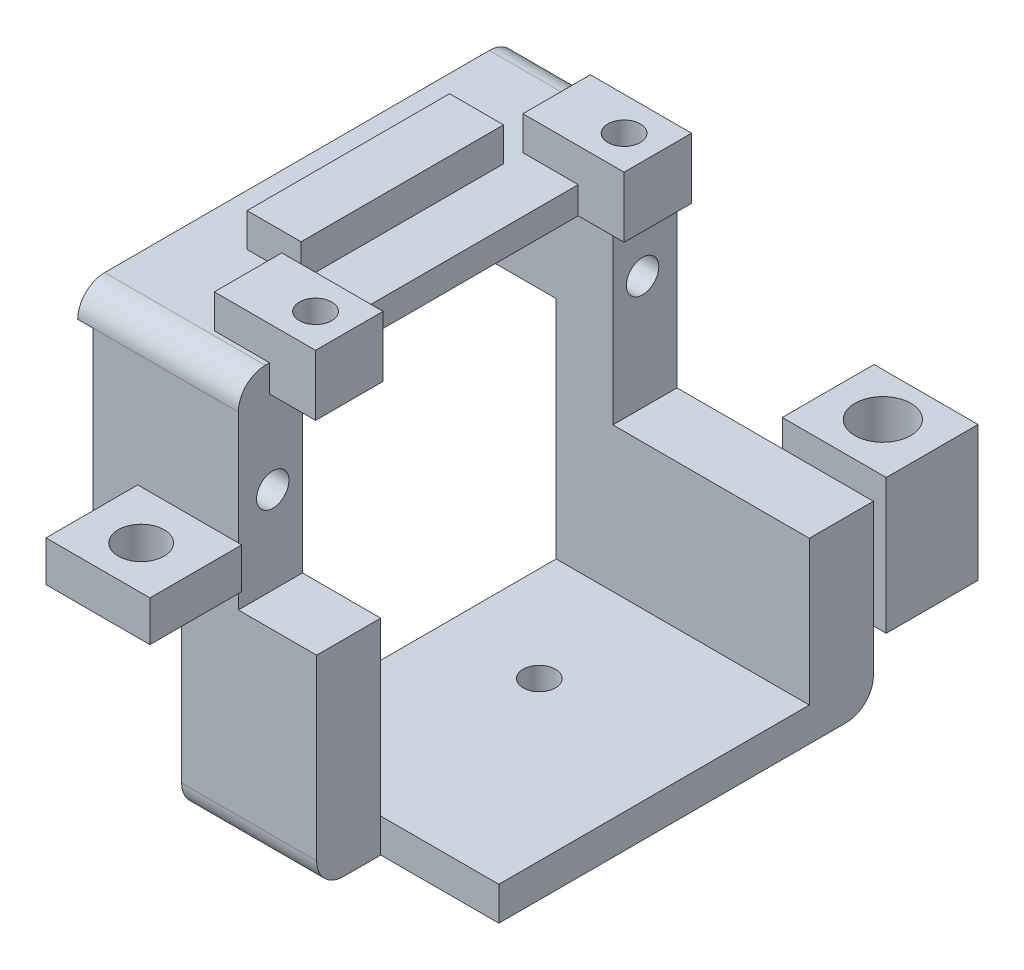
SolidWorks part; units mm, degrees
ref_plane "Front Plane" through (0, 0, 0) normal (0, 0, 1) x (1, 0, 0)
ref_plane "Top Plane" through (0, 0, 0) normal (0, 1, 0) x (1, 0, 0)
ref_plane "Right Plane" through (0, 0, 0) normal (1, 0, 0) x (0, 0, -1)
sketch "Sketch1" plane through (0, 0, 0) normal (0, 1, 0) x (1, 0, 0)
  line L0 (-1.1, 16.25) -> (-1.1, 11.5)
  line L1 (-17.65, -16.25) -> (17.65, -16.25)
  line L2 (-17.65, -16.25) -> (-17.65, 16.25)
  line L3 (-17.65, 16.25) -> (17.65, 16.25)
  line L4 (17.65, -16.25) -> (17.65, 16.25)
  line L5 (-17.65, -16.25) -> (17.65, 16.25) construction
  line L6 (-17.65, 16.25) -> (17.65, -16.25) construction
  line L7 (-1.1, 11.5) -> (17.65, 11.5)
  line L8 (-1.1, -16.25) -> (-1.1, -11.5)
  line L9 (-1.1, -11.5) -> (17.65, -11.5)
  line L10 (-1.1, 11.5) -> (-1.1, -11.5) construction
  line L11 (8.9, -11.5) -> (8.9, -16.25)
  line L12 (-8.8, 16.25) -> (-8.8, 11.5)
  line L13 (-8.8, 11.5) -> (-3.8, 11.5)
  line L14 (-3.8, 11.5) -> (-3.8, 16.25)
  line L15 (-3.8, -16.25) -> (-3.8, -11.5)
  line L16 (-3.8, -11.5) -> (-8.8, -11.5)
  line L17 (-8.8, -11.5) -> (-8.8, -16.25)
  line L18 (-8.8, 11.5) -> (-8.8, -11.5)
  line L19 (18.6, 16.25) -> (18.6, 23.05)
  line L20 (18.6, 23.05) -> (10.9, 23.05)
  line L21 (10.9, 23.05) -> (10.9, 16.25)
  line L22 (-4.35, -16.25) -> (-4.35, -23.05)
  line L23 (-4.35, -23.05) -> (3.35, -23.05)
  line L24 (3.35, -23.05) -> (3.35, -16.25)
  line L25 (18.6, 16.25) -> (10.9, 16.25)
  line L28 (-1.1, 11.5) -> (-1.1, -11.5)
  circle A0 centre (14.75, 19.85) radius 2.075
  circle A2 centre (-0.5, -19.85) radius 1.7
  point P0 (0, 0)
  point P11 (-1.1, 0)
  point P31 (14.75, 23.05)
  point P45 (-0.5, -23.05)
  dimension "D11" = 4.15
  dimension "D19" = 3.4
  dimension "D1" = 32.5
  dimension "D2" = 23
  dimension "D3" = 8.75
  dimension "D4" = 10
  dimension "D5" = 16.55
  dimension "D6" = 2.7
  dimension "D7" = 5
  dimension "D8" = 14.75
  dimension "D9" = 7.7
  dimension "D10" = 6.8
  dimension "D12" = 0.5
  dimension "D13" = 19.85
  dimension "D16" = 7.7
  dimension "D17" = 6.8
  dimension "D20" = 19.85
extrude "Boss-Extrude1" add sketch "Sketch1" against normal blind 2.5 contours L7 L28 L9 L4 | L0 L7 L4 L3 | L11 L9 L8 L1 region at (8.275, 0, -13.875) region at (8.275, 0, 0) region at (3.9, 0, 13.875)
extrude "Boss-Extrude2" add sketch "Sketch1<3>" along normal blind 12.7 contours L0 L7 L4 L3 | L11 L9 L8 L1 region at (8.275, 0, -13.875) region at (3.9, 0, 13.875)
sketch "Sketch1<3>" plane through (0, 0, 0) normal (0, 1, 0) x (1, 0, 0) same geometry as "Sketch1"
sketch "Sketch3" plane through (0, 0, 0) normal (0, 1, 0) x (1, 0, 0)
  line L0 (3.1, 16.25) -> (3.1, 11.5)
  line L1 (-17.65, 16.25) -> (17.65, 16.25) construction
  line L2 (-1.1, 11.5) -> (17.65, 11.5) construction
  line L3 (3.1, 11.5) -> (-17.65, 11.5)
  line L4 (-17.65, -16.25) -> (-17.65, 16.25) construction
  line L5 (3.1, -16.25) -> (3.1, -11.5)
  line L6 (-17.65, -16.25) -> (17.65, -16.25) construction
  line L7 (-1.1, -11.5) -> (17.65, -11.5) construction
  line L8 (3.1, -11.5) -> (-17.65, -11.5)
  line L9 (3.1, 11.5) -> (3.1, -11.5)
  line L10 (-7.65, -11.5) -> (-7.65, -16.275)
  line L11 (3.1, 16.25) -> (-17.65, 16.25)
  line L12 (-17.65, 16.25) -> (-17.65, 11.5)
  line L13 (-17.65, -11.5) -> (-17.65, -16.25)
  line L14 (-17.65, -16.25) -> (3.1, -16.25)
  line L15 (-8.8, 11.5) -> (-8.8, -11.5)
  line L16 (-8.8, 11.5) -> (-8.8, 16.25)
  line L17 (-8.8, -11.5) -> (-8.8, -16.25)
  dimension "D1" = 20.75
  dimension "D2" = 10
extrude "Boss-Extrude3" add sketch "Sketch3" along normal blind 12.7 from surface contours L11 L12 L3 L0 | L10 L14 L5 L8 region at (-2.85, 0, -13.875) region at (-2.275, 0, 13.875) starting at face at (8.275, 12.7, -13.875)
extrude "Boss-Extrude4" add sketch "Sketch3<3>" along normal blind 2 from surface contours L16 L3 L0 L11 | L3 L15 L8 L9 | L10 L14 L5 L8 | L8 L17 L14 L10 region at (-2.85, 0, -13.875) region at (-2.85, 0, 0) region at (-2.275, 0, 13.875) region at (-8.225, 0, 13.875) starting at face at (-2.275, 25.4, 13.875)
sketch "Sketch3<3>" plane through (0, 0, 0) normal (0, 1, 0) x (1, 0, 0) same geometry as "Sketch3"
sketch "Sketch2" plane through (0, 0, 0) normal (1, 0, 0) x (0, 0, -1)
  line L0 (13.7, 6.45) -> (-13.7, 6.45) construction
  line L1 (-13.7, 19.15) -> (13.7, 19.15) construction
  circle A0 centre (13.7, 6.45) radius 1.2
  circle A1 centre (-13.7, 6.45) radius 1.2
  circle A2 centre (-13.7, 19.15) radius 1.2
  circle A3 centre (13.7, 19.15) radius 1.2
  point P4 (0, 6.45)
  dimension "D1" = 2.4
  dimension "D2" = 2.4
  dimension "D6" = 2.4
  dimension "D7" = 2.4
  dimension "D3" = 27.4
  dimension "D4" = 6.45
  dimension "D5" = 6.45
extrude "Cut-Extrude1" cut sketch "Sketch2" along normal blind 8 from surface contours A1 | A0 region at (0, 6.45, -13.7) region at (0, 6.45, 13.7) starting at face at (-1.1, 5.725, 0)
extrude "Cut-Extrude2" cut sketch "Sketch2<3>" against normal blind 8 from surface contours A3 | A2 region at (0, 19.15, 13.7) region at (0, 19.15, -13.7) starting at face at (3.1, 19.55, 0)
sketch "Sketch2<3>" plane through (0, 0, 0) normal (1, 0, 0) x (0, 0, -1) same geometry as "Sketch2"
extrude "Boss-Extrude5" add sketch "Sketch1<4>" against normal blind 3 from offset 17 contours L23 L24 L1 L22 A2 region at (1.125, 0, 16.3527)
sketch "Sketch1<4>" plane through (0, 0, 0) normal (0, 1, 0) x (1, 0, 0) same geometry as "Sketch1"
extrude "Boss-Extrude6" add sketch "Sketch1<7>" against normal blind 10 from surface contours L20 L21 L3 L19 A0 region at (11.0027, 0, -19.65) starting at face at (10.375, 12.7, -13.875)
sketch "Sketch1<7>" plane through (0, 0, 0) normal (0, 1, 0) x (1, 0, 0) same geometry as "Sketch1"
fillet "Fillet1" radius 2 4 edges at (3.9, -2.5, 16.25) (-2.85, 27.4, 16.25) (8.275, -2.5, -16.25) (-2.85, 27.4, -16.25)
sketch "Sketch5" plane through (0, 0, 0) normal (0, 1, 0) x (1, 0, 0)
  line L1 (17.65, 16.25) -> (3.1, 16.25)
  line L2 (17.65, 16.25) -> (17.65, 11.5)
  line L3 (17.65, 11.5) -> (3.1, 11.5)
  line L4 (3.1, 16.25) -> (3.1, 11.5)
extrude "Cut-Extrude3" cut sketch "Sketch5" against normal blind 2 from surface starting at face at (12.5625, 12.7, -16.7625)
sketch "Sketch6" plane through (0, 0, 0) normal (0, 1, 0) x (1, 0, 0)
  line L1 (-8.8, 11.5) -> (-1.1, 11.5)
  line L2 (-8.8, 11.5) -> (-8.8, 16.25)
  line L3 (-8.8, 16.25) -> (-1.1, 16.25)
  line L4 (-1.1, 11.5) -> (-1.1, 16.25)
extrude "Cut-Extrude4" cut sketch "Sketch6" along normal blind 4 from surface starting at face at (-4.95, 12.7, -13.875)
sketch "Sketch7" plane through (0, 0, 0) normal (0, 1, 0) x (1, 0, 0)
  line L0 (4, 11.43) -> (4, -11.43) construction
  line L2 (1.5, 13.93) -> (6.5, 13.93)
  line L3 (1.5, 13.93) -> (1.5, 8.93)
  line L4 (1.5, 8.93) -> (6.5, 8.93)
  line L5 (6.5, 13.93) -> (6.5, 8.93)
  line L6 (1.5, 13.93) -> (6.5, 8.93) construction
  line L7 (1.5, 8.93) -> (6.5, 13.93) construction
  line L8 (1.5, -8.93) -> (6.5, -8.93)
  line L9 (1.5, -8.93) -> (1.5, -13.93)
  line L10 (1.5, -13.93) -> (6.5, -13.93)
  line L11 (6.5, -8.93) -> (6.5, -13.93)
  line L12 (1.5, -8.93) -> (6.5, -13.93) construction
  line L13 (1.5, -13.93) -> (6.5, -8.93) construction
  line L21 (-5, -7.5) -> (-1, -7.5)
  line L22 (-5, -7.5) -> (-5, 7.5)
  line L23 (-5, 7.5) -> (-1, 7.5)
  line L24 (-1, -7.5) -> (-1, 7.5)
  line L25 (-5, -7.5) -> (-1, 7.5) construction
  line L26 (-5, 7.5) -> (-1, -7.5) construction
  line L27 (1.5, 13.93) -> (-1, 13.93)
  line L28 (1.5, 13.93) -> (1.5, 8.93)
  line L29 (1.5, 8.93) -> (-1, 8.93)
  line L30 (-1, 13.93) -> (-1, 8.93)
  line L31 (1.5, -13.93) -> (-1, -13.93)
  line L32 (1.5, -13.93) -> (1.5, -8.93)
  line L33 (1.5, -8.93) -> (-1, -8.93)
  line L34 (-1, -13.93) -> (-1, -8.93)
  circle A0 centre (4, 11.43) radius 1.2
  circle A1 centre (4, -11.43) radius 1.2
  point P4 (4, 0)
  point P14 (-3, 0)
  dimension "D1" = 2.4
  dimension "D2" = 2.4
  dimension "D3" = 22.86
  dimension "D4" = 5
  dimension "D5" = 5
  dimension "D6" = 5
  dimension "D7" = 5
  dimension "D8" = 4
  dimension "D9" = 3
  dimension "D10" = 15
  dimension "D11" = 4
extrude "Boss-Extrude7" add sketch "Sketch7" along normal blind 2.5 and the other way blind 2 from surface contours L21 L24 L23 L22 | L11 L8 L9 L10 A1 | L34 L31 L9 L33 | L27 L30 L29 L3 | L5 L2 L3 L4 A0 region at (4, 0, -13.8593) region at (0.25, 0, -11.43) region at (4, 0, 9.0007) region at (0.25, 0, 11.43) region at (-3, 0, 0) starting at face at (-2.85, 27.4, 0)
sketch "Sketch8" plane through (0, 0, 0) normal (0, 1, 0) x (1, 0, 0)
  line L2 (-17.65, -16.25) -> (17.65, -16.25) construction
  line L3 (8.45, 5.7) -> (3.45, 5.7)
  line L4 (8.45, 5.7) -> (8.45, 0.7)
  line L5 (8.45, 0.7) -> (3.45, 0.7)
  line L6 (3.45, 5.7) -> (3.45, 0.7)
  line L7 (8.45, 5.7) -> (3.45, 0.7) construction
  line L8 (8.45, 0.7) -> (3.45, 5.7) construction
  line L11 (-1.1, 11.5) -> (-1.1, -11.5) construction
  circle A0 centre (5.95, 3.2) radius 1.2
  dimension "D3" = 2.4
  dimension "D1" = 7.05
  dimension "D2" = 19.45
  dimension "D4" = 5
  dimension "D5" = 5
extrude "Boss-Extrude8" add sketch "Sketch8" against normal blind 4.1 from surface starting at face at (8.4833, -2.5, 3.8333)
extrude "Cut-Extrude5" cut sketch "Sketch8<2>" against normal through all both contours A0 region at (5.95, 0, -3.2)
sketch "Sketch8<2>" plane through (0, 0, 0) normal (0, 1, 0) x (1, 0, 0) same geometry as "Sketch8"
extrude "Cut-Extrude6" cut sketch "Sketch7<4>" along normal up to surface (29.9 mm away) from surface contours A0 | A1 region at (4, 0, -11.43) region at (4, 0, 11.43) up to face at (4, 29.9, 10.23) starting at face at (1.5722, 25.4, 1.8056)
sketch "Sketch7<4>" plane through (0, 0, 0) normal (0, 1, 0) x (1, 0, 0) same geometry as "Sketch7"
